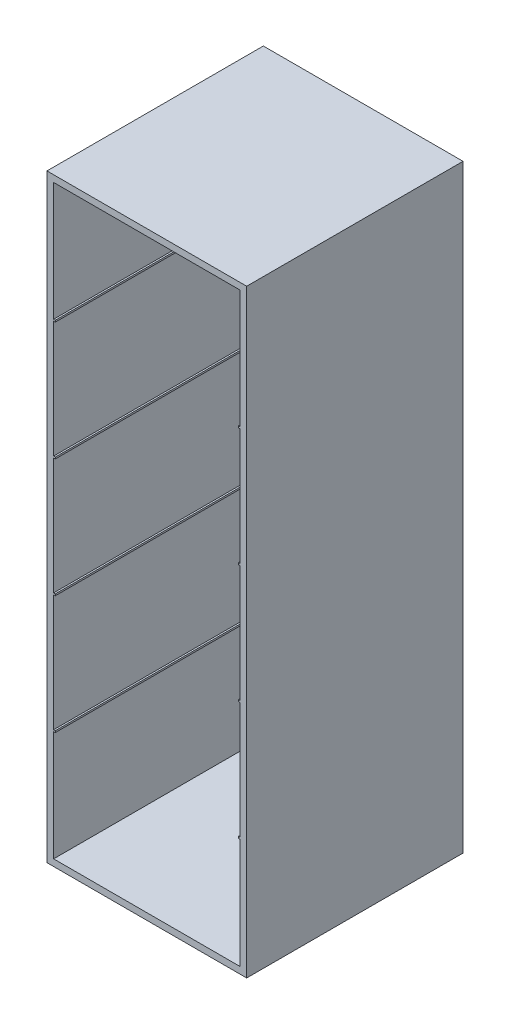
SolidWorks part; units mm, degrees
ref_plane "Front Plane" through (0, 0, 0) normal (0, 0, 1) x (1, 0, 0)
ref_plane "Top Plane" through (0, 0, 0) normal (0, 1, 0) x (1, 0, 0)
ref_plane "Right Plane" through (0, 0, 0) normal (1, 0, 0) x (0, 0, -1)
sketch "Sketch1" plane through (0, 0, 0) normal (0, 0, 1) x (1, 0, 0)
  line L1 (300, -900) -> (-300, -900)
  line L2 (300, -900) -> (300, 900)
  line L3 (300, 900) -> (-300, 900)
  line L4 (-300, -900) -> (-300, 900)
  line L5 (300, -900) -> (-300, 900) construction
  line L6 (300, 900) -> (-300, -900) construction
  point P0 (0, 0)
  dimension "D1" = 1800
  dimension "D2" = 600
extrude "Boss-Extrude1" add sketch "Sketch1" along normal blind 650
shell "Shell1" thickness 20 removed face at (0, 0, 650)
sketch "Sketch2" plane through (0, 0, 650) normal (0, 0, 1) x (1, 0, 0)
  line L0 (280, 880) -> (-280, 880) construction
  line L1 (0, 1176.5174) -> (0, -1168.3887) construction
  line L2 (280, 544) -> (-280, 544)
  line L3 (280, 188) -> (-280, 188)
  line L4 (280, 188) -> (280, 168)
  line L5 (280, 188) -> (-280, 188)
  line L6 (280, 544) -> (-280, 544)
  line L7 (280, 544) -> (280, 524)
  line L8 (280, 524) -> (-280, 524)
  line L9 (-280, 544) -> (-280, 524)
  line L10 (280, 524) -> (275, 524)
  line L11 (280, 524) -> (280, 519)
  line L12 (280, 519) -> (275, 519)
  line L13 (275, 524) -> (275, 519)
  line L14 (-280, 524) -> (-275, 524)
  line L15 (-280, 524) -> (-280, 519)
  line L16 (-280, 519) -> (-275, 519)
  line L17 (-275, 524) -> (-275, 519)
  line L18 (280, -880) -> (280, 880) construction
  line L19 (-280, 880) -> (-280, -880) construction
  line L20 (280, 168) -> (-280, 168)
  line L21 (-280, 188) -> (-280, 168)
  line L22 (280, 168) -> (275, 168)
  line L23 (280, 168) -> (280, 163)
  line L24 (280, 163) -> (275, 163)
  line L25 (275, 168) -> (275, 163)
  line L26 (280, -168) -> (-280, -168)
  line L27 (280, -524) -> (-280, -524)
  line L28 (280, -168) -> (-280, -168)
  line L29 (280, -168) -> (280, -188)
  line L30 (280, -188) -> (-280, -188)
  line L31 (-280, -168) -> (-280, -188)
  line L32 (280, -188) -> (275, -188)
  line L33 (280, -188) -> (280, -193)
  line L34 (280, -193) -> (275, -193)
  line L35 (275, -188) -> (275, -193)
  line L37 (280, -524) -> (-280, -524)
  line L38 (280, -524) -> (280, -544)
  line L39 (280, -544) -> (-280, -544)
  line L40 (-280, -524) -> (-280, -544)
  line L41 (280, -544) -> (275, -544)
  line L42 (280, -544) -> (280, -549)
  line L43 (280, -549) -> (275, -549)
  line L44 (275, -544) -> (275, -549)
  line M24 (280, 880) -> (280, -880)
  dimension "D1" = 336
  dimension "D2" = 20
  dimension "D3" = 5
  dimension "D4" = 336
  dimension "D5" = 20
  dimension "D6" = 5
  dimension "D7" = 5
  dimension "D8" = 336
  dimension "D9" = 20
  dimension "D10" = 5
  dimension "D11" = 5
  dimension "D12" = 336
  dimension "D13" = 20
  dimension "D14" = 5
  dimension "D15" = 5
extrude "Boss-Extrude2" add sketch "Sketch2" against normal up to next contours L8 L13 L12 M24 | L20 L25 L24 M24 | L30 L35 L34 M24 | L39 L44 L43 M24 region at (277.5, 521.5, 650) region at (277.5, 165.5, 650) region at (277.5, -190.5, 650) region at (277.5, -546.5, 650)
sketch "Sketch3" plane through (0, 0, 650) normal (0, 0, 1) x (1, 0, 0)
  line L0 (0, 1173.1856) -> (0, -1169.2047) construction
mirror "Mirror1" about plane through (0, 0, 0) normal (1, 0, 0) of "Boss-Extrude2"
